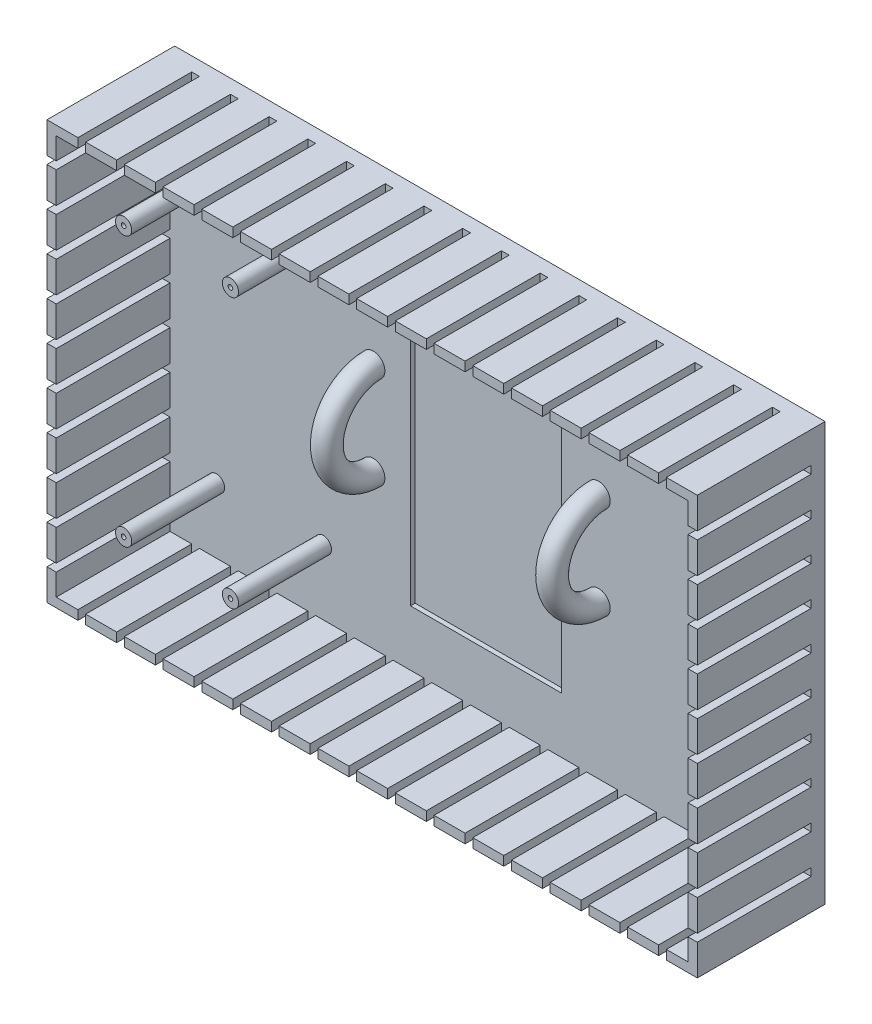
SolidWorks part; units mm, degrees
ref_plane "Front Plane" through (0, 0, 0) normal (1, 0, 0) x (0, 1, 0)
ref_plane "Top Plane" through (0, 0, 0) normal (0, 0, 1) x (0, 1, 0)
ref_plane "Right Plane" through (0, 0, 0) normal (0, 1, 0) x (-1, 0, 0)
sketch "Sketch1" plane through (0, 0, 0) normal (0, 0, 1) x (0, 1, 0)
  line L0 (-45, 0) -> (45, 0) construction
  line L1 (45, -70) -> (-45, -70)
  line L2 (45, -70) -> (45, 70)
  line L3 (45, 70) -> (-45, 70)
  line L4 (-45, -70) -> (-45, 70)
  line L5 (0, 70) -> (0, -70) construction
  point P9 (0, 0)
  dimension "D1" = 140
  dimension "D2" = 90
extrude "Boss-Extrude1" add sketch "Sketch1" along normal blind 3
sketch "Sketch2" plane through (0, 0, 3) normal (0, 0, 1) x (1, 0, 0)
  line L0 (-70, 45) -> (-70, -45) construction
  line L1 (-16.25, 31) -> (16.25, 31)
  line L2 (-16.25, 31) -> (-16.25, -31)
  line L3 (-16.25, -31) -> (16.25, -31)
  line L4 (16.25, 31) -> (16.25, -31)
  line L6 (-70, 0) -> (-16.25, 0) construction
  line L7 (16.25, 0) -> (70, 0) construction
  line L8 (70, -45) -> (70, 45) construction
  line L9 (0, 31) -> (0, 45) construction
  line L10 (70, 45) -> (-70, 45) construction
  line L11 (0, -31) -> (0, -45) construction
  line L12 (-70, -45) -> (70, -45) construction
  dimension "D1" = 62
  dimension "D2" = 32.5
extrude "Cut-Extrude1" cut sketch "Sketch2" against normal blind 1
sketch "Sketch6" plane through (0, 0, 3) normal (0, 0, 1) x (1, 0, 0)
  line L0 (-58, -45) -> (-58, -29) construction
  line L1 (-70, -45) -> (70, -45) construction
  line L2 (-58, 29) -> (-58, 45) construction
  line L3 (70, 45) -> (-70, 45) construction
  line L4 (-70, 45) -> (-70, -45) construction
  circle A0 centre (-58, 29) radius 1.75
  circle A1 centre (-35, 29) radius 1.75
  circle A2 centre (-35, -29) radius 1.75
  circle A3 centre (-58, -29) radius 1.75
  circle A4 centre (-58, 29) radius 0.5
  circle A5 centre (-35, 29) radius 0.5
  circle A6 centre (-58, -29) radius 0.5
  circle A7 centre (-35, -29) radius 0.5
  dimension "D1" = 3.5
  dimension "D2" = 23
  dimension "D3" = 58
  dimension "D4" = 12
  dimension "D5" = 1
extrude "Boss-Extrude2" add sketch "Sketch6" along normal blind 20 contours A1 | A0 | A3 | A2 region at (-59.7005, 29, 3) region at (-36.7005, 29, 3) region at (-36.7005, -29, 3) region at (-59.7005, -29, 3)
extrude "Boss-Extrude3" add sketch "Sketch6<3>" along normal blind 19 contours A4 | A5 | A6 | A7 region at (-58, 29, 3) region at (-35, 29, 3) region at (-58, -29, 3) region at (-35, -29, 3)
sketch "Sketch6<3>" plane through (0, 0, 3) normal (0, 0, 1) x (1, 0, 0) same geometry as "Sketch6"
sketch "Sketch7" plane through (0, 0, 3) normal (0, 0, 1) x (1, 0, 0)
  line L0 (-61.6667, 45) -> (-61.6667, 43)
  line L1 (-70, 45) -> (-63.3333, 45)
  line L2 (-70, 45) -> (-70, 43)
  line L3 (-70, 43) -> (-63.3333, 43)
  line L4 (-63.3333, 45) -> (-63.3333, 43)
  line L5 (-61.6667, 45) -> (-55, 45)
  line L6 (-55, 45) -> (-55, 43)
  line L7 (-61.6667, 43) -> (-55, 43)
  line L8 (-53.3333, 45) -> (-53.3333, 43)
  line L9 (-53.3333, 45) -> (-46.6667, 45)
  line L10 (-46.6667, 45) -> (-46.6667, 43)
  line L11 (-53.3333, 43) -> (-46.6667, 43)
  line L12 (-45, 45) -> (-45, 43)
  line L13 (-45, 45) -> (-38.3333, 45)
  line L14 (-38.3333, 45) -> (-38.3333, 43)
  line L15 (-45, 43) -> (-38.3333, 43)
  line L16 (-36.6667, 45) -> (-36.6667, 43)
  line L17 (-36.6667, 45) -> (-30, 45)
  line L18 (-30, 45) -> (-30, 43)
  line L19 (-36.6667, 43) -> (-30, 43)
  line L20 (-28.3333, 45) -> (-28.3333, 43)
  line L21 (-28.3333, 45) -> (-21.6667, 45)
  line L22 (-21.6667, 45) -> (-21.6667, 43)
  line L23 (-28.3333, 43) -> (-21.6667, 43)
  line L24 (-20, 45) -> (-20, 43)
  line L25 (-20, 45) -> (-13.3333, 45)
  line L26 (-13.3333, 45) -> (-13.3333, 43)
  line L27 (-20, 43) -> (-13.3333, 43)
  line L28 (-11.6667, 45) -> (-11.6667, 43)
  line L29 (-11.6667, 45) -> (-5, 45)
  line L30 (-5, 45) -> (-5, 43)
  line L31 (-11.6667, 43) -> (-5, 43)
  line L32 (-3.3333, 45) -> (-3.3333, 43)
  line L33 (-3.3333, 45) -> (3.3333, 45)
  line L34 (3.3333, 45) -> (3.3333, 43)
  line L35 (-3.3333, 43) -> (3.3333, 43)
  line L36 (5, 45) -> (5, 43)
  line L37 (5, 45) -> (11.6667, 45)
  line L38 (11.6667, 45) -> (11.6667, 43)
  line L39 (5, 43) -> (11.6667, 43)
  line L40 (13.3333, 45) -> (13.3333, 43)
  line L41 (13.3333, 45) -> (20, 45)
  line L42 (20, 45) -> (20, 43)
  line L43 (13.3333, 43) -> (20, 43)
  line L44 (21.6667, 45) -> (21.6667, 43)
  line L45 (21.6667, 45) -> (28.3333, 45)
  line L46 (28.3333, 45) -> (28.3333, 43)
  line L47 (21.6667, 43) -> (28.3333, 43)
  line L48 (30, 45) -> (30, 43)
  line L49 (30, 45) -> (36.6667, 45)
  line L50 (36.6667, 45) -> (36.6667, 43)
  line L51 (30, 43) -> (36.6667, 43)
  line L52 (38.3333, 45) -> (38.3333, 43)
  line L53 (38.3333, 45) -> (45, 45)
  line L54 (45, 45) -> (45, 43)
  line L55 (38.3333, 43) -> (45, 43)
  line L56 (46.6667, 45) -> (46.6667, 43)
  line L57 (46.6667, 45) -> (53.3333, 45)
  line L58 (53.3333, 45) -> (53.3333, 43)
  line L59 (46.6667, 43) -> (53.3333, 43)
  line L60 (55, 45) -> (55, 43)
  line L61 (55, 45) -> (61.6667, 45)
  line L62 (61.6667, 45) -> (61.6667, 43)
  line L63 (55, 43) -> (61.6667, 43)
  line L64 (63.3333, 45) -> (63.3333, 43)
  line L65 (63.3333, 45) -> (70, 45)
  line L66 (70, 45) -> (70, 43)
  line L67 (63.3333, 43) -> (70, 43)
  line L68 (-70, 36.6667) -> (-70, 30)
  line L69 (-70, 45) -> (-68, 45)
  line L70 (-70, 45) -> (-70, 38.3333)
  line L71 (-70, 38.3333) -> (-68, 38.3333)
  line L72 (-68, 45) -> (-68, 38.3333)
  line L73 (-70, 36.6667) -> (-68, 36.6667)
  line L74 (-68, 36.6667) -> (-68, 30)
  line L75 (-70, 30) -> (-68, 30)
  line L76 (-70, 28.3333) -> (-70, 21.6667)
  line L77 (-70, 28.3333) -> (-68, 28.3333)
  line L78 (-68, 28.3333) -> (-68, 21.6667)
  line L79 (-70, 21.6667) -> (-68, 21.6667)
  line L80 (-70, 20) -> (-70, 13.3333)
  line L81 (-70, 20) -> (-68, 20)
  line L82 (-68, 20) -> (-68, 13.3333)
  line L83 (-70, 13.3333) -> (-68, 13.3333)
  line L84 (-70, 11.6667) -> (-70, 5)
  line L85 (-70, 11.6667) -> (-68, 11.6667)
  line L86 (-68, 11.6667) -> (-68, 5)
  line L87 (-70, 5) -> (-68, 5)
  line L88 (-70, 3.3333) -> (-70, -3.3333)
  line L89 (-70, 3.3333) -> (-68, 3.3333)
  line L90 (-68, 3.3333) -> (-68, -3.3333)
  line L91 (-70, -3.3333) -> (-68, -3.3333)
  line L92 (-70, -5) -> (-70, -11.6667)
  line L93 (-70, -5) -> (-68, -5)
  line L94 (-68, -5) -> (-68, -11.6667)
  line L95 (-70, -11.6667) -> (-68, -11.6667)
  line L96 (-70, -13.3333) -> (-70, -20)
  line L97 (-70, -13.3333) -> (-68, -13.3333)
  line L98 (-68, -13.3333) -> (-68, -20)
  line L99 (-70, -20) -> (-68, -20)
  line L100 (-70, -21.6667) -> (-70, -28.3333)
  line L101 (-70, -21.6667) -> (-68, -21.6667)
  line L102 (-68, -21.6667) -> (-68, -28.3333)
  line L103 (-70, -28.3333) -> (-68, -28.3333)
  line L104 (-70, -30) -> (-70, -36.6667)
  line L105 (-70, -30) -> (-68, -30)
  line L106 (-68, -30) -> (-68, -36.6667)
  line L107 (-70, -36.6667) -> (-68, -36.6667)
  line L108 (-70, -38.3333) -> (-70, -45)
  line L109 (-70, -38.3333) -> (-68, -38.3333)
  line L110 (-68, -38.3333) -> (-68, -45)
  line L111 (-70, -45) -> (-68, -45)
  line L112 (0, 0) -> (0, 18.2112) construction
  line L113 (0, 0) -> (-20.7335, 0) construction
  line L114 (13.3333, -45) -> (20, -45)
  line L115 (20, -45) -> (20, -43)
  line L116 (13.3333, -43) -> (20, -43)
  line L117 (13.3333, -45) -> (13.3333, -43)
  line L118 (21.6667, -45) -> (28.3333, -45)
  line L119 (28.3333, -45) -> (28.3333, -43)
  line L120 (21.6667, -43) -> (28.3333, -43)
  line L121 (21.6667, -45) -> (21.6667, -43)
  line L122 (30, -45) -> (36.6667, -45)
  line L123 (36.6667, -45) -> (36.6667, -43)
  line L124 (30, -43) -> (36.6667, -43)
  line L125 (30, -45) -> (30, -43)
  line L126 (38.3333, -45) -> (45, -45)
  line L127 (45, -45) -> (45, -43)
  line L128 (38.3333, -43) -> (45, -43)
  line L129 (38.3333, -45) -> (38.3333, -43)
  line L130 (46.6667, -45) -> (53.3333, -45)
  line L131 (53.3333, -45) -> (53.3333, -43)
  line L132 (46.6667, -43) -> (53.3333, -43)
  line L133 (46.6667, -45) -> (46.6667, -43)
  line L134 (55, -45) -> (61.6667, -45)
  line L135 (61.6667, -45) -> (61.6667, -43)
  line L136 (55, -43) -> (61.6667, -43)
  line L137 (55, -45) -> (55, -43)
  line L138 (63.3333, -45) -> (70, -45)
  line L139 (70, -45) -> (70, -43)
  line L140 (63.3333, -43) -> (70, -43)
  line L141 (63.3333, -45) -> (63.3333, -43)
  line L142 (5, -45) -> (11.6667, -45)
  line L143 (11.6667, -45) -> (11.6667, -43)
  line L144 (5, -43) -> (11.6667, -43)
  line L145 (5, -45) -> (5, -43)
  line L146 (-3.3333, -45) -> (3.3333, -45)
  line L147 (3.3333, -45) -> (3.3333, -43)
  line L148 (-3.3333, -43) -> (3.3333, -43)
  line L149 (-3.3333, -45) -> (-3.3333, -43)
  line L150 (-11.6667, -45) -> (-5, -45)
  line L151 (-5, -45) -> (-5, -43)
  line L152 (-11.6667, -43) -> (-5, -43)
  line L153 (-11.6667, -45) -> (-11.6667, -43)
  line L154 (-20, -45) -> (-13.3333, -45)
  line L155 (-13.3333, -45) -> (-13.3333, -43)
  line L156 (-20, -43) -> (-13.3333, -43)
  line L157 (-20, -45) -> (-20, -43)
  line L158 (-28.3333, -45) -> (-21.6667, -45)
  line L159 (-21.6667, -45) -> (-21.6667, -43)
  line L160 (-28.3333, -43) -> (-21.6667, -43)
  line L161 (-28.3333, -45) -> (-28.3333, -43)
  line L162 (-36.6667, -45) -> (-30, -45)
  line L163 (-30, -45) -> (-30, -43)
  line L164 (-36.6667, -43) -> (-30, -43)
  line L165 (-36.6667, -45) -> (-36.6667, -43)
  line L166 (-70, -43) -> (-63.3333, -43)
  line L167 (-63.3333, -45) -> (-63.3333, -43)
  line L168 (-70, -45) -> (-63.3333, -45)
  line L169 (-70, -45) -> (-70, -43)
  line L170 (-61.6667, -45) -> (-55, -45)
  line L171 (-55, -45) -> (-55, -43)
  line L172 (-61.6667, -43) -> (-55, -43)
  line L173 (-61.6667, -45) -> (-61.6667, -43)
  line L174 (-53.3333, -45) -> (-46.6667, -45)
  line L175 (-46.6667, -45) -> (-46.6667, -43)
  line L176 (-53.3333, -43) -> (-46.6667, -43)
  line L177 (-53.3333, -45) -> (-53.3333, -43)
  line L178 (-45, -45) -> (-38.3333, -45)
  line L179 (-38.3333, -45) -> (-38.3333, -43)
  line L180 (-45, -43) -> (-38.3333, -43)
  line L181 (-45, -45) -> (-45, -43)
  line L182 (70, 28.3333) -> (68, 28.3333)
  line L183 (68, 28.3333) -> (68, 21.6667)
  line L184 (70, 21.6667) -> (68, 21.6667)
  line L185 (70, 28.3333) -> (70, 21.6667)
  line L186 (70, 36.6667) -> (68, 36.6667)
  line L187 (68, 36.6667) -> (68, 30)
  line L188 (70, 30) -> (68, 30)
  line L189 (70, 36.6667) -> (70, 30)
  line L190 (70, 38.3333) -> (68, 38.3333)
  line L191 (68, 45) -> (68, 38.3333)
  line L192 (70, 45) -> (68, 45)
  line L193 (70, 45) -> (70, 38.3333)
  line L194 (70, 20) -> (68, 20)
  line L195 (68, 20) -> (68, 13.3333)
  line L196 (70, 13.3333) -> (68, 13.3333)
  line L197 (70, 20) -> (70, 13.3333)
  line L198 (70, 11.6667) -> (68, 11.6667)
  line L199 (68, 11.6667) -> (68, 5)
  line L200 (70, 5) -> (68, 5)
  line L201 (70, 11.6667) -> (70, 5)
  line L202 (70, 3.3333) -> (68, 3.3333)
  line L203 (68, 3.3333) -> (68, -3.3333)
  line L204 (70, -3.3333) -> (68, -3.3333)
  line L205 (70, 3.3333) -> (70, -3.3333)
  line L206 (70, -5) -> (68, -5)
  line L207 (68, -5) -> (68, -11.6667)
  line L208 (70, -11.6667) -> (68, -11.6667)
  line L209 (70, -5) -> (70, -11.6667)
  line L210 (70, -13.3333) -> (68, -13.3333)
  line L211 (68, -13.3333) -> (68, -20)
  line L212 (70, -20) -> (68, -20)
  line L213 (70, -13.3333) -> (70, -20)
  line L214 (70, -21.6667) -> (68, -21.6667)
  line L215 (68, -21.6667) -> (68, -28.3333)
  line L216 (70, -28.3333) -> (68, -28.3333)
  line L217 (70, -21.6667) -> (70, -28.3333)
  line L218 (70, -30) -> (68, -30)
  line L219 (68, -30) -> (68, -36.6667)
  line L220 (70, -36.6667) -> (68, -36.6667)
  line L221 (70, -30) -> (70, -36.6667)
  line L222 (70, -38.3333) -> (68, -38.3333)
  line L223 (68, -38.3333) -> (68, -45)
  line L224 (70, -45) -> (68, -45)
  line L225 (70, -38.3333) -> (70, -45)
  point P225 (0, 0)
  line M13 (70, 45) -> (-70, 45)
  line M14 (-70, 45) -> (-70, -45)
  line M15 (-70, -45) -> (70, -45)
  line M16 (70, -45) -> (70, 45)
  dimension "D1" = 6.6667
  dimension "D2" = 2
  dimension "D3" = 17
  dimension "D4" = 11
extrude "Boss-Extrude6" add sketch "Sketch7" along normal blind 24.5 contours L107 L106 L105 M14 | L166 L110 L109 M14 | L72 L3 L71 M14 | L75 L74 L73 M14 | L79 L78 L77 M14 | L83 L82 L81 M14 | L95 L94 L93 M14 | L173 L171 L172 M15 | L177 L175 L176 M15 | L181 L179 L180 M15 | L165 L163 L164 M15 | L157 L155 L156 M15 | L153 L151 L152 M15 | L149 L147 L148 M15 | L117 L115 L116 M15 | L121 L119 L120 M15 | L125 L123 L124 M15 | L137 L135 L136 M15 | L222 L223 L140 M16 | L140 L223 L138 M16 | L223 L140 L141 M15 | L67 L191 L190 M16 | L188 L186 L187 M16 | L196 L194 L195 M16 | L200 L198 L199 M16 | L204 L202 L203 M16 | L208 L206 L207 M16 | L212 L210 L211 M16 | L72 L1 L3 M14 | L0 L7 L6 M13 | L8 L11 L10 M13 | L12 L15 L14 M13 | L20 L23 L22 M13 | L24 L27 L26 M13 | L56 L59 L58 M13 | L52 L55 L54 M13 | L48 L51 L50 M13 | L40 L43 L42 M13 | L36 L39 L38 M13 | L32 L35 L34 M13 | L28 L31 L30 M13 | L60 L63 L62 M13 | L100 L103 L102 L101 | L169 L166 L167 L168 | L84 L87 L86 L85 | L89 L90 L91 L88 | L97 L98 L99 L96 | L159 L160 L161 L158 | L142 L143 L144 L145 | L126 L127 L128 L129 | L130 L131 L132 L133 | L66 L67 L64 L65 | L185 L184 L183 L182 | L214 L215 L216 L217 | L218 L219 L220 L221 | L1 L4 L3 L2 | L18 L19 L16 L17 | L45 L46 L47 L44 region at (-58.3333, 44, 3) region at (-50, 44, 3) region at (-69, 44, 3) region at (-69, 40.6667, 3) region at (-41.6667, 44, 3) region at (-69, 33.3333, 3) region at (-25, 44, 3) region at (-69, 25, 3) region at (-16.6667, 44, 3) region at (-69, 16.6667, 3) region at (-8.3333, 44, 3) region at (0, 44, 3) region at (8.3333, 44, 3) region at (-69, -8.3333, 3) region at (16.6667, 44, 3) region at (33.3333, 44, 3) region at (-69, -33.3333, 3) region at (41.6667, 44, 3) region at (-69, -40.6667, 3) region at (50, 44, 3) region at (58.3333, 44, 3) region at (-58.3333, -44, 3) region at (-50, -44, 3) region at (69, 40.6667, 3) region at (-41.6667, -44, 3) region at (69, 33.3333, 3) region at (-33.3333, -44, 3) region at (69, 16.6667, 3) region at (-16.6667, -44, 3) region at (69, 8.3333, 3) region at (-8.3333, -44, 3) region at (69, 0, 3) region at (0, -44, 3) region at (69, -8.3333, 3) region at (69, -16.6667, 3) region at (16.6667, -44, 3) region at (25, -44, 3) region at (33.3333, -44, 3) region at (69, -40.6667, 3) region at (69, -44, 3) region at (65.6667, -44, 3) region at (58.3333, -44, 3)
sketch "Sketch9" plane through (0, 0, 3) normal (0, 0, 1) x (1, 0, 0)
  line L0 (-36.3093, 0) -> (22.5747, 0) construction
  line L1 (0, 0) -> (0, 22.2066) construction
  line L2 (-16.25, 31) -> (-16.25, -31) construction
  circle A0 centre (-24.25, -10) radius 2.5
  circle A1 centre (24.25, -10) radius 2.5
  point P7 (-25.9339, -10)
  dimension "D1" = 5
  dimension "D2" = 10
  dimension "D3" = 8
revolve "Revolve3" add sketch "Sketch9" angle 180 about L0 reverse direction yes
